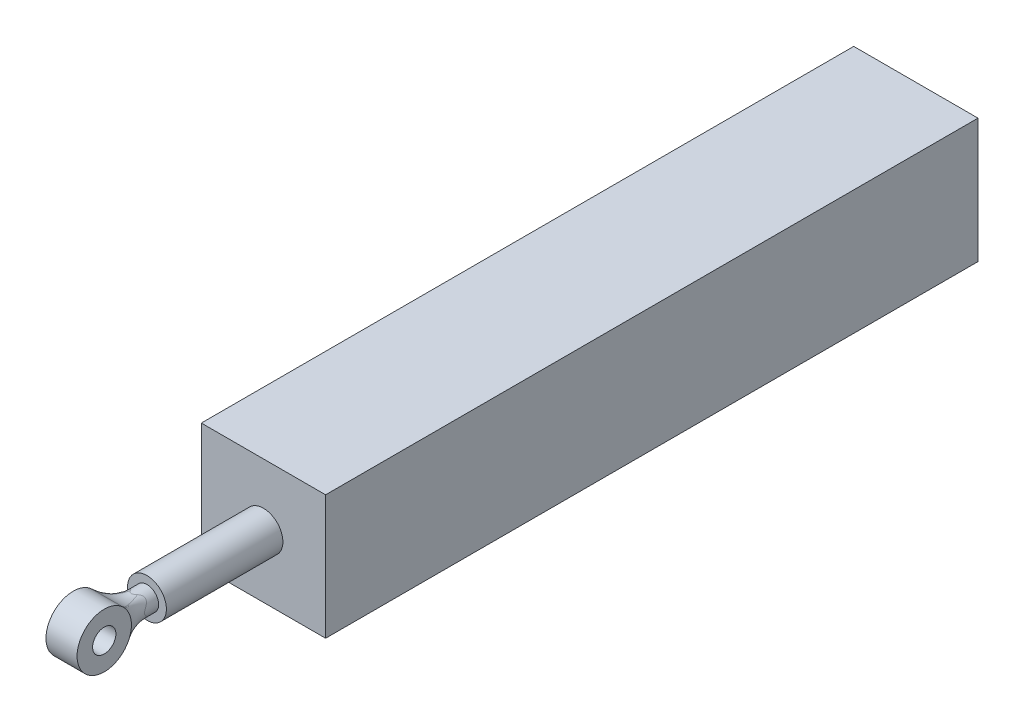
SolidWorks part; units mm, degrees
ref_plane "Front Plane" through (0, 0, 0) normal (0, 0, 1) x (1, 0, 0)
ref_plane "Top Plane" through (0, 0, 0) normal (0, 1, 0) x (1, 0, 0)
ref_plane "Right Plane" through (0, 0, 0) normal (1, 0, 0) x (0, 0, -1)
sketch "Sketch1" plane through (0, 0, 0) normal (0, 0, 1) x (1, 0, 0)
  line L1 (-16, -16) -> (16, -16)
  line L2 (-16, -16) -> (-16, 16)
  line L3 (-16, 16) -> (16, 16)
  line L4 (16, -16) -> (16, 16)
  line L5 (-16, -16) -> (16, 16) construction
  line L6 (-16, 16) -> (16, -16) construction
  point P0 (0, 0)
  dimension "D1" = 32
  dimension "D2" = 32
extrude "Boss-Extrude1" add sketch "Sketch1" along normal blind 168
sketch "Sketch3" plane through (0, 0, 168) normal (0, 0, 1) x (1, 0, 0)
  circle A0 centre (0, 0) radius 5
  dimension "D1" = 10
extrude "Boss-Extrude2" add sketch "Sketch3" along normal blind 30
sketch "Sketch4" plane through (0, 0, 198) normal (0, 0, 1) x (1, 0, 0)
  circle A0 centre (0, 0) radius 3
  dimension "D1" = 6
extrude "Boss-Extrude3" add sketch "Sketch4" along normal blind 15
sketch "Sketch6" plane through (0, 0, 0) normal (1, 0, 0) x (0, 0, -1)
  line L0 (-213, 3) -> (-213, -3) construction
  circle A0 centre (-213, 0) radius 7
  circle A1 centre (-213, 0) radius 3
  dimension "D1" = 6
  dimension "D2" = 14
extrude "Boss-Extrude4" add sketch "Sketch6" along normal mid plane 8
sketch "Sketch7" plane through (4, 0, 0) normal (1, 0, 0) x (0, 0, -1)
  circle A0 centre (-213, 0) radius 3 construction
  circle A1 centre (-213, 0) radius 3
extrude "Cut-Extrude1" cut sketch "Sketch7" against normal mid plane 46
fillet "Fillet1" radius 10 1 edges at (2.9733, 0.3996, 206.0114)
